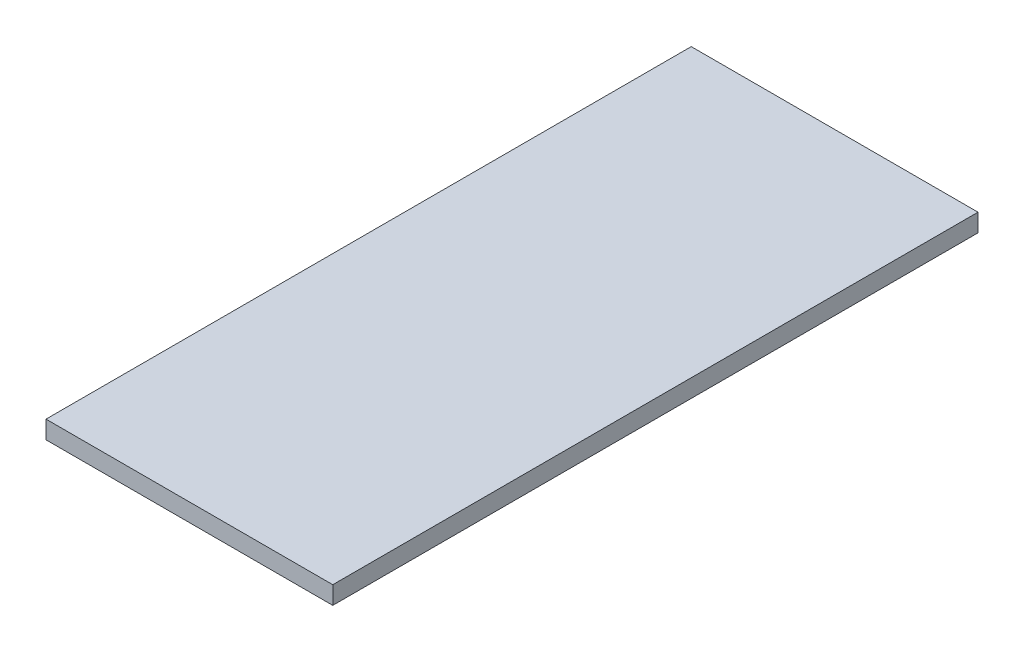
SolidWorks part; units mm, degrees
material "ABS PC"
ref_plane "X-Y Datum" through (0, 0, 0) normal (0, 0, 1) x (1, 0, 0)
ref_plane "X-Z Datum" through (0, 0, 0) normal (0, 1, 0) x (1, 0, 0)
ref_plane "Y-Z Datum" through (0, 0, 0) normal (1, 0, 0) x (0, 0, -1)
sketch "Sketch1" plane through (0, 0, 0) normal (0, 0, 1) x (1, 0, 0)
  line L1 (-50.8, -3.175) -> (50.8, -3.175)
  line L2 (-50.8, -3.175) -> (-50.8, 3.175)
  line L3 (-50.8, 3.175) -> (50.8, 3.175)
  line L4 (50.8, -3.175) -> (50.8, 3.175)
  line L5 (-50.8, -3.175) -> (50.8, 3.175) construction
  line L6 (-50.8, 3.175) -> (50.8, -3.175) construction
  point P0 (0, 0)
  dimension "D1" = 6.35
  dimension "D2" = 101.6
extrude "Boss-Extrude1" add sketch "Sketch1" along normal blind 228.6
